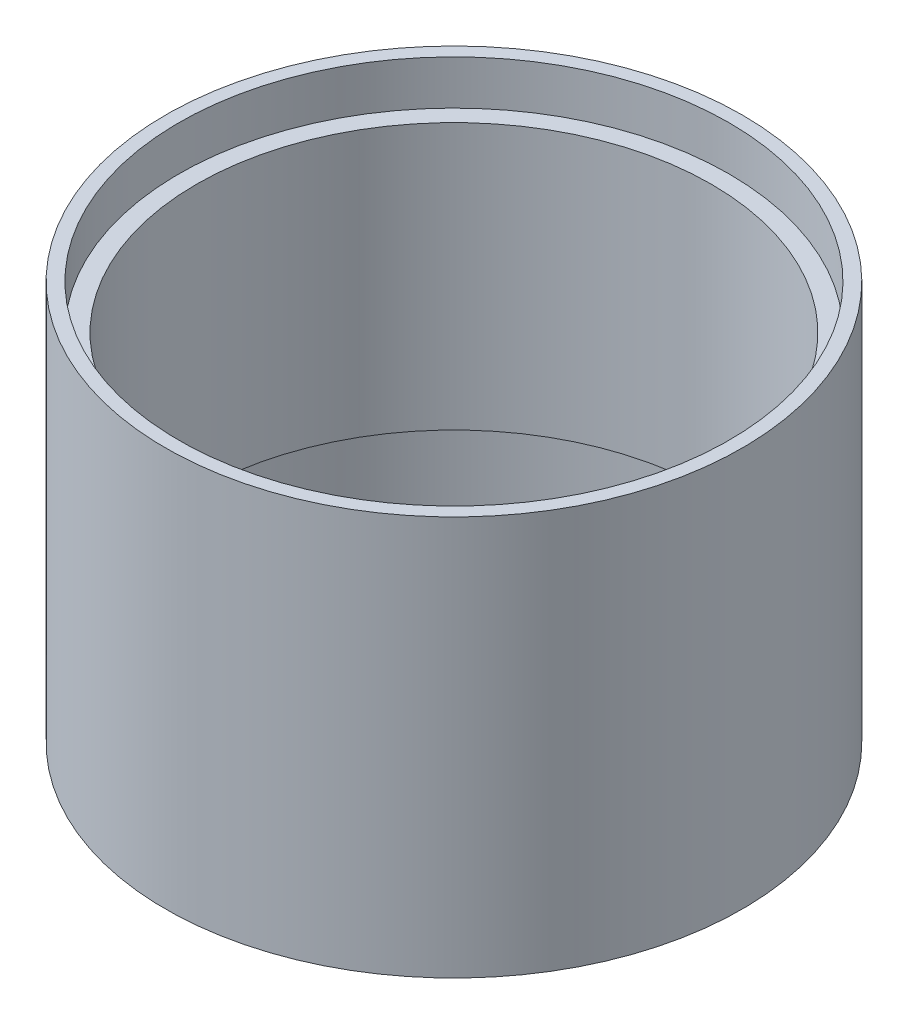
SolidWorks part; units mm, degrees
material "HYPALON"
ref_plane "Front Plane" through (0, 0, 0) normal (0, 0, 1) x (1, 0, 0)
ref_plane "Top Plane" through (0, 0, 0) normal (0, 1, 0) x (1, 0, 0)
ref_plane "Right Plane" through (0, 0, 0) normal (1, 0, 0) x (0, 0, -1)
sketch "Szkic1" plane through (0, 0, 0) normal (0, 0, 1) x (1, 0, 0)
  line L0 (0, 0) -> (-65, 0)
  line L1 (-65, 0) -> (-65, 20)
  line L2 (-62, 20) -> (-58, 20)
  line L3 (-58, 20) -> (-58, 80)
  line L4 (-62, 20) -> (-62, 0)
  line L5 (-58, 80) -> (-62, 80)
  line L6 (-65, 90) -> (-62, 90)
  line L7 (-65, 20) -> (-65, 90)
  line L8 (-62, 90) -> (-62, 80)
  line L13 (0, 0) -> (0, 22.4148)
  point P5 (-62.019, 86.6624)
  dimension "D1" = 65
  dimension "D2" = 20
  dimension "D3" = 7
  dimension "D4" = 3
  dimension "D5" = 3
  dimension "D6" = 10
  dimension "D7" = 90
revolve "Obrót1" add sketch "Szkic1" angle 360 about L13 region at (-61.8529, 47.3529, 0)
